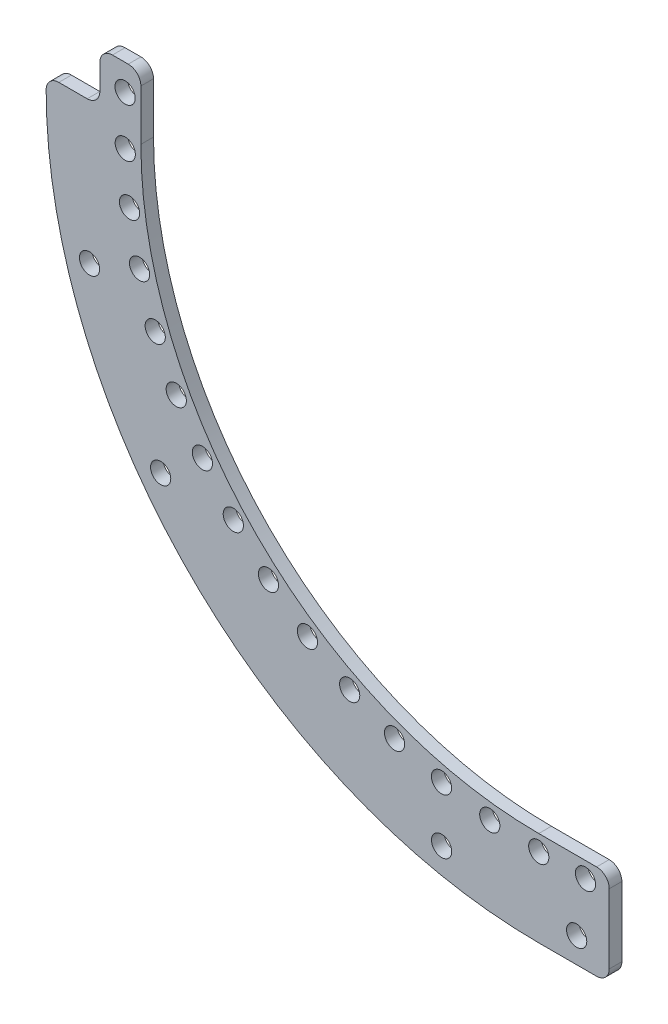
SolidWorks part; units mm, degrees
material "A-玻璃纤维"
ref_plane "前视基准面" through (0, 0, 0) normal (0, 0, 1) x (1, 0, 0)
ref_plane "上视基准面" through (0, 0, 0) normal (0, 1, 0) x (1, 0, 0)
ref_plane "右视基准面" through (0, 0, 0) normal (1, 0, 0) x (0, 0, -1)
sketch "草图1" plane through (0, 0, 0) normal (0, 0, 1) x (1, 0, 0)
  line L0 (-139.1546, 76.5) -> (-139.1546, -33.6254) construction
  line L1 (-91.6495, 50) -> (0, 50) construction
  line L2 (-90.2793, 53) -> (-5.3283, 53) construction
  line L4 (-99.1546, 26.5) -> (0, 26.5) construction
  line L6 (-99.1546, 26.5) -> (-88, 26.5) construction
  line L7 (0, 26.5) -> (0, 0) construction
  line L8 (-88, 26.5) -> (-88, -20.8435) construction
  arc A0 (-139.1546, 66.5) -> (-99.1546, 26.5) centre (-99.1546, 66.5) ccw
  dimension "D1" = 3
  dimension "D4" = 80
  dimension "D3" = 23.5
  dimension "D7" = 10
  dimension "D8" = 88
  dimension "D9" = 11.1546
sketch "草图2" plane through (0, 0, 0) normal (0, 0, 1) x (1, 0, 0)
  line L0 (0, 0) -> (-88, 0) construction
  line L1 (-88, 26.5) -> (-88, -20.8435) construction
  line L2 (0, 3) -> (-88, 3) construction
  line L3 (-99.1546, 26.5) -> (0, 26.5) construction
  line L4 (-139.1546, 76.5) -> (-139.1546, -33.6254) construction
  line L5 (-99.1546, 26.5) -> (-88, 26.5) construction
  line L6 (-139.1546, 76.5) -> (-139.1546, 66.5) construction
  line L7 (-88, 3) -> (-88, 26.5) construction
  line L8 (-161.1546, 76.5) -> (-161.1546, 66.5) construction
  line L9 (-99.1546, 4.5) -> (-88, 4.5) construction
  line L10 (-117.1546, 76.5) -> (-117.1546, 66.5) construction
  line L11 (-99.1546, 48.5) -> (-88, 48.5) construction
  line L13 (-162.1546, 76.5) -> (-162.1546, 66.5)
  line L14 (-99.1546, 3.5) -> (-88, 3.5)
  line L15 (-164.6546, 76.5) -> (-164.6546, 66.5) construction
  line L16 (-99.1546, 1) -> (-88, 1) construction
  line L17 (-169.1546, 76.5) -> (-169.1546, 66.5) construction
  line L18 (-99.1546, -3.5) -> (-88, -3.5) construction
  line L19 (-177.1546, 76.5) -> (-177.1546, 66.5)
  line L20 (-99.1546, -11.5) -> (-88, -11.5)
  line L21 (-177.1546, 76.5) -> (-162.1546, 76.5)
  line L22 (-88, 3.5) -> (-88, -11.5)
  line L23 (-99.1546, 66.5) -> (-99.1546, 1) construction
  line L24 (-99.1546, 66.5) -> (-106.9101, 1.4608) construction
  line L25 (-164.6546, 75.2931) -> (-164.6546, 78.7931) construction
  line L26 (-99.1546, 66.5) -> (-99.1546, 1) construction
  line L27 (-99.1546, 66.5) -> (-106.9101, 1.4608) construction
  arc A0 (-139.1546, 66.5) -> (-99.1546, 26.5) centre (-99.1546, 66.5) ccw construction
  arc A1 (-139.1546, 66.5) -> (-99.1546, 26.5) centre (-99.1546, 66.5) ccw construction
  arc A2 (-161.1546, 66.5) -> (-99.1546, 4.5) centre (-99.1546, 66.5) ccw construction
  arc A3 (-117.1546, 66.5) -> (-99.1546, 48.5) centre (-99.1546, 66.5) ccw construction
  arc A4 (-162.1546, 66.5) -> (-99.1546, 3.5) centre (-99.1546, 66.5) ccw
  arc A5 (-164.6546, 66.5) -> (-99.1546, 1) centre (-99.1546, 66.5) ccw construction
  arc A6 (-169.1546, 66.5) -> (-99.1546, -3.5) centre (-99.1546, 66.5) ccw construction
  arc A7 (-177.1546, 66.5) -> (-99.1546, -11.5) centre (-99.1546, 66.5) ccw
  circle A8 centre (-91.7546, 1) radius 3.5 construction
  circle A9 centre (-99.1546, 1) radius 3.5 construction
  circle A10 centre (-106.9101, 1.4608) radius 3.5 construction
  circle A11 centre (-114.5564, 2.8366) radius 3.5 construction
  circle A12 centre (-121.9861, 5.108) radius 3.5 construction
  circle A13 centre (-129.0945, 8.2432) radius 3.5 construction
  circle A14 centre (-135.7817, 12.198) radius 3.5 construction
  circle A15 centre (-141.9536, 16.9168) radius 3.5 construction
  circle A16 centre (-147.5234, 22.3332) radius 3.5 construction
  circle A17 centre (-152.4127, 28.3709) radius 3.5 construction
  circle A18 centre (-156.5527, 34.9451) radius 3.5 construction
  circle A19 centre (-159.8851, 41.9633) radius 3.5 construction
  circle A20 centre (-162.3632, 49.3266) radius 3.5 construction
  circle A21 centre (-163.9519, 56.9316) radius 3.5 construction
  circle A22 centre (-164.6291, 64.6711) radius 3.5 construction
  circle A23 centre (-164.6546, 72.3711) radius 3.5 construction
  arc A24 (-139.1546, 66.5) -> (-99.1546, 26.5) centre (-99.1546, 66.5) ccw construction
  circle A26 centre (-91.7546, 1) radius 1.6
  circle A27 centre (-99.1546, 1) radius 1.6
  circle A28 centre (-106.9101, 1.4608) radius 1.6
  circle A29 centre (-114.5564, 2.8366) radius 1.6
  circle A30 centre (-121.9861, 5.108) radius 1.6
  circle A31 centre (-129.0945, 8.2432) radius 1.6
  circle A32 centre (-135.7817, 12.198) radius 1.6
  circle A33 centre (-141.9536, 16.9168) radius 1.6
  circle A34 centre (-147.5234, 22.3332) radius 1.6
  circle A35 centre (-152.4127, 28.3709) radius 1.6
  circle A36 centre (-156.5527, 34.9451) radius 1.6
  circle A37 centre (-159.8851, 41.9633) radius 1.6
  circle A38 centre (-162.3632, 49.3266) radius 1.6
  circle A39 centre (-163.9519, 56.9316) radius 1.6
  circle A40 centre (-164.6291, 64.6711) radius 1.6
  circle A41 centre (-164.6546, 72.3711) radius 1.6
  dimension "D8" = 7
  dimension "D9" = 7
  dimension "D10" = 7.4
  dimension "D13" = 7
  dimension "D16" = 3.2
  dimension "D17" = 3.2
  dimension "D20" = 3.2
  dimension "D1" = 3
  dimension "D2" = 22
  dimension "D4" = 1
  dimension "D12" = 6.8
  dimension "D14" = 7.7691
  dimension "D15" = 7.7
  dimension "D19" = 6.8
  dimension "D3" = 22
  dimension "D5" = 3.5
  dimension "D6" = 7
  dimension "D7" = 8
  dimension "D11" = 14
  dimension "D18" = 14
extrude "凸台-拉伸1" add sketch "草图2" along normal blind 2
sketch "草图3" plane through (0, 0, 2) normal (0, 0, 1) x (1, 0, 0)
  line L0 (0, 0) -> (-88, 0) construction
  line L1 (-88, 26.5) -> (-88, -20.8435) construction
  line L2 (-88, 0) -> (-88, -3) construction
  line L3 (-88, -3) -> (-79.8645, -3) construction
  line L4 (-177.1546, 76.5) -> (-177.1546, 66.5) construction
  line L5 (-99.1546, -11.5) -> (-88, -11.5) construction
  line L6 (-177.1546, 76.5) -> (-177.1546, 66.5) construction
  line L7 (-99.1546, -11.5) -> (-88, -11.5) construction
  line L8 (-173.1546, 76.5) -> (-173.1546, 66.5) construction
  line L9 (-99.1546, -7.5) -> (-88, -7.5) construction
  arc A0 (-177.1546, 66.5) -> (-99.1546, -11.5) centre (-99.1546, 66.5) ccw construction
  arc A1 (-177.1546, 66.5) -> (-99.1546, -11.5) centre (-99.1546, 66.5) ccw construction
  arc A2 (-173.1546, 66.5) -> (-99.1546, -7.5) centre (-99.1546, 66.5) ccw construction
  dimension "D2" = 4
  dimension "D1" = 3
sketch "草图4" plane through (0, 0, 2) normal (0, 0, 1) x (1, 0, 0)
  line L0 (-181.7432, 78.5) -> (-173.2222, 78.5) construction
  line L1 (-162.1546, 76.5) -> (-177.1546, 76.5) construction
  line L2 (-187.8077, 70) -> (-181.0523, 70) construction
  line L3 (-177.1546, 68.5) -> (-168.6546, 68.5)
  line L4 (-177.1546, 76.5) -> (-177.1546, 66.5) construction
  line L5 (-168.6546, 68.5) -> (-168.6546, 76.5)
  line L6 (-168.6546, 76.5) -> (-177.1546, 76.5)
  line L7 (-177.1546, 76.5) -> (-177.1546, 68.5)
  circle A0 centre (-164.6546, 72.3711) radius 3.5 construction
  dimension "D5" = 7
  dimension "D1" = 2
  dimension "D2" = 8.5
  dimension "D3" = 1.5
  dimension "D4" = 8.5
extrude "切除-拉伸1" cut sketch "草图4" against normal blind 3
sketch "草图6" plane through (0, 0, 2) normal (0, 0, 1) x (1, 0, 0)
  line L0 (-99.1546, -7.5) -> (-88, -7.5) construction
  line L1 (-99.1546, -11.5) -> (-99.1546, 66.5) construction
  line L2 (-99.1546, 66.5) -> (-114.5401, -5.8829) construction
  line L3 (-159.0218, 23.0039) -> (-99.1546, 66.5) construction
  line L4 (-99.1546, 66.5) -> (-170.288, 46.1028) construction
  line L5 (-99.1546, 66.5) -> (-194.6638, 66.5) construction
  circle A0 centre (-170.288, 46.1028) radius 1.6
  arc A1 (-173.1546, 66.5) -> (-99.1546, -7.5) centre (-99.1546, 66.5) ccw construction
  circle A2 centre (-159.0218, 23.0039) radius 1.6
  circle A3 centre (-114.5401, -5.8829) radius 1.6
  circle A4 centre (-93.1546, -7.5) radius 1.6
  dimension "D1" = 3.2
  dimension "D2" = 3.2
  dimension "D3" = 3.2
  dimension "D4" = 3.2
  dimension "D8" = 6
  dimension "D5" = 16
  dimension "D6" = 20
  dimension "D7" = 12
extrude "切除-拉伸2" cut sketch "草图6" against normal blind 10
fillet "圆角1" radius 2 1 edges at (-168.6546, 68.5, 1)
fillet "圆角2" radius 2 5 edges at (-168.6546, 76.5, 1) (-162.1546, 76.5, 1) (-88, 3.5, 1) (-88, -11.5, 1) (-177.1546, 68.5, 1)
